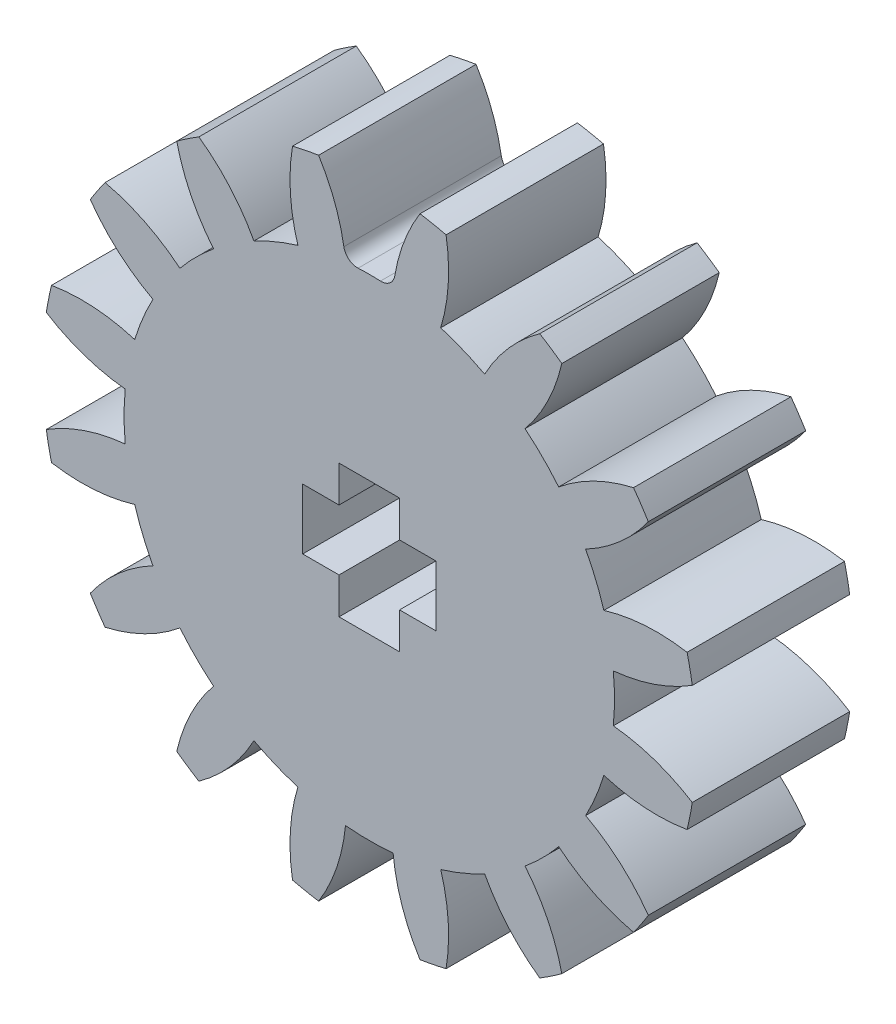
SolidWorks part; units mm, degrees
ref_plane "Front Plane" through (0, 0, 0) normal (0, 0, 1) x (1, 0, 0)
ref_plane "Top Plane" through (0, 0, 0) normal (0, 1, 0) x (1, 0, 0)
ref_plane "Right Plane" through (0, 0, 0) normal (1, 0, 0) x (0, 0, -1)
sketch "Sketch1" plane through (0, 0, 0) normal (0, 0, 1) x (1, 0, 0)
  line L0 (1.25, 1.25) -> (2.75, 1.25)
  line L3 (-1.25, 2.75) -> (1.25, 2.75)
  line L6 (-1.25, 2.75) -> (-1.25, 1.25)
  line L7 (-1.25, -2.75) -> (1.25, -2.75)
  line L8 (1.25, 2.75) -> (1.25, 1.25)
  line L9 (-1.25, 2.75) -> (1.25, -2.75) construction
  line L10 (-1.25, -2.75) -> (1.25, 2.75) construction
  line L11 (-2.75, 1.25) -> (-1.25, 1.25)
  line L12 (-2.75, 1.25) -> (-2.75, -1.25)
  line L13 (-2.75, -1.25) -> (-1.25, -1.25)
  line L14 (2.75, 1.25) -> (2.75, -1.25)
  line L15 (-2.75, 1.25) -> (2.75, -1.25) construction
  line L16 (-2.75, -1.25) -> (2.75, 1.25) construction
  line L17 (1.25, -1.25) -> (1.25, -2.75)
  line L18 (1.25, -1.25) -> (2.75, -1.25)
  line L19 (-1.25, -1.25) -> (-1.25, -2.75)
  circle A0 centre (0, 0) radius 13.5
  point P7 (0, 0)
  point P8 (0, 0)
  point P13 (0, 0)
  dimension "D2" = 27
  dimension "D1" = 5.5
  dimension "D3" = 2.5
extrude "Boss-Extrude1" add sketch "Sketch1" along normal mid plane 6.5 contours A0 region at (-13.1182, 0, 0)
sketch "Sketch2" plane through (0, 0, 0) normal (0, 0, 1) x (1, 0, 0)
  line L0 (0, 0) -> (0, 13.5) construction
  line L1 (0, 0) -> (-0.9822, 10.0772) construction
  line L2 (0, 8.0719) -> (-4.2467, 19.7397) construction
  arc A0 (1.3999, 11.9181) -> (-1.3999, 11.9181) centre (0, 0) ccw construction
  arc A1 (0.9822, 10.0772) -> (-0.9822, 10.0772) centre (0, 0) ccw
  arc A3 (2.0928, 13.3368) -> (-2.0928, 13.3368) centre (0, 0) ccw
  arc A4 (-0.9822, 10.0772) -> (-2.0928, 13.3368) centre (-8.4601, 9.3484) ccw
  arc A5 (0.9822, 10.0772) -> (2.0928, 13.3368) centre (8.4601, 9.3484) cw
  circle A6 centre (0, 0) radius 13.5 construction
  dimension "D1" = 24
  dimension "D2" = 3.375
  dimension "D3" = 20
  dimension "D4" = 2.8062
extrude "Cut-Extrude1" cut sketch "Sketch2" against normal through all both and the other way through all
fillet "Fillet1" radius 0.57 2 edges at (0.9822, 10.0772, 0) (-0.9822, 10.0772, 0)
pattern_circular "CirPattern3" count 16 over 360 about axis through (0, 0, 3.25) along (0, 0, -1) of "Cut-Extrude1"
equation "\"Module\"= 1.5"
equation "\"Pressure Angle\"= 20"
equation "\"Bore\"= 2"
equation "\"NumTeeth\"= 16"
equation "\"D2@Sketch1\"=(\"NumTeeth\"+2)*\"Module\""
equation "\"D1@Sketch2\"=\"NumTeeth\"*\"Module\""
equation "\"ToothDepth\"= IIF ( \"Module\" < 1.25 , 2.4 * \"Module\" , 2.25 * \"Module\" )"
equation "\"D2@Sketch2\"=\"ToothDepth\""
equation "\"D3@Sketch2\"=\"Pressure Angle\""
equation "\"D4@Sketch2\"=((\"Module\"*PI)/2)+0.3*\"Module\""
equation "\"D1@Fillet1\"=\"Module\"*0.38"
equation "\"D1@CirPattern3\"=\"NumTeeth\""
